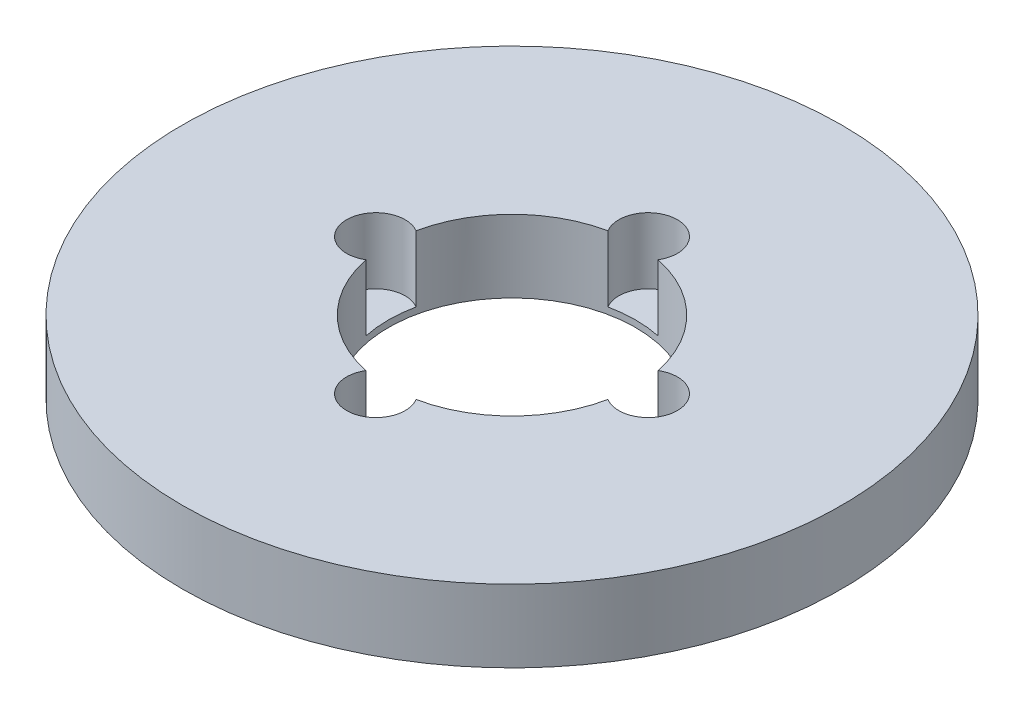
SolidWorks part; units mm, degrees
ref_plane "Front Plane" through (0, 0, 0) normal (0, 0, 1) x (1, 0, 0)
ref_plane "Top Plane" through (0, 0, 0) normal (0, 1, 0) x (1, 0, 0)
ref_plane "Right Plane" through (0, 0, 0) normal (1, 0, 0) x (0, 0, -1)
sketch "Sketch1" plane through (0, 0, 0) normal (0, 1, 0) x (1, 0, 0)
  circle A0 centre (0, 0) radius 100
  dimension "FLANGE_OD" = 200
extrude "Boss-Extrude1" add sketch "Sketch1" along normal blind 22
sketch "Sketch2" plane through (0, 0, 0) normal (0, 1, 0) x (1, 0, 0)
  circle A0 centre (0, 0) radius 37.5
  dimension "BORE_D" = 75
extrude "Cut-Extrude1" cut sketch "Sketch2" along normal through all
sketch "Sketch3" plane through (0, 22, 0) normal (0, 1, 0) x (1, 0, 0)
  circle A0 centre (0, 0) radius 41.2975 construction
  circle A1 centre (-41.2975, 0) radius 8.8793
  dimension "BOLT_D" = 17.7586
  dimension "BOLT_PCD" = 82.5951
extrude "Cut-Extrude2" cut sketch "Sketch3" against normal blind 20.0064
pattern_circular "CirPattern1" count 4 over 360 about axis through (0, 0, 0) along (0, 1, 0) of "Cut-Extrude2"
